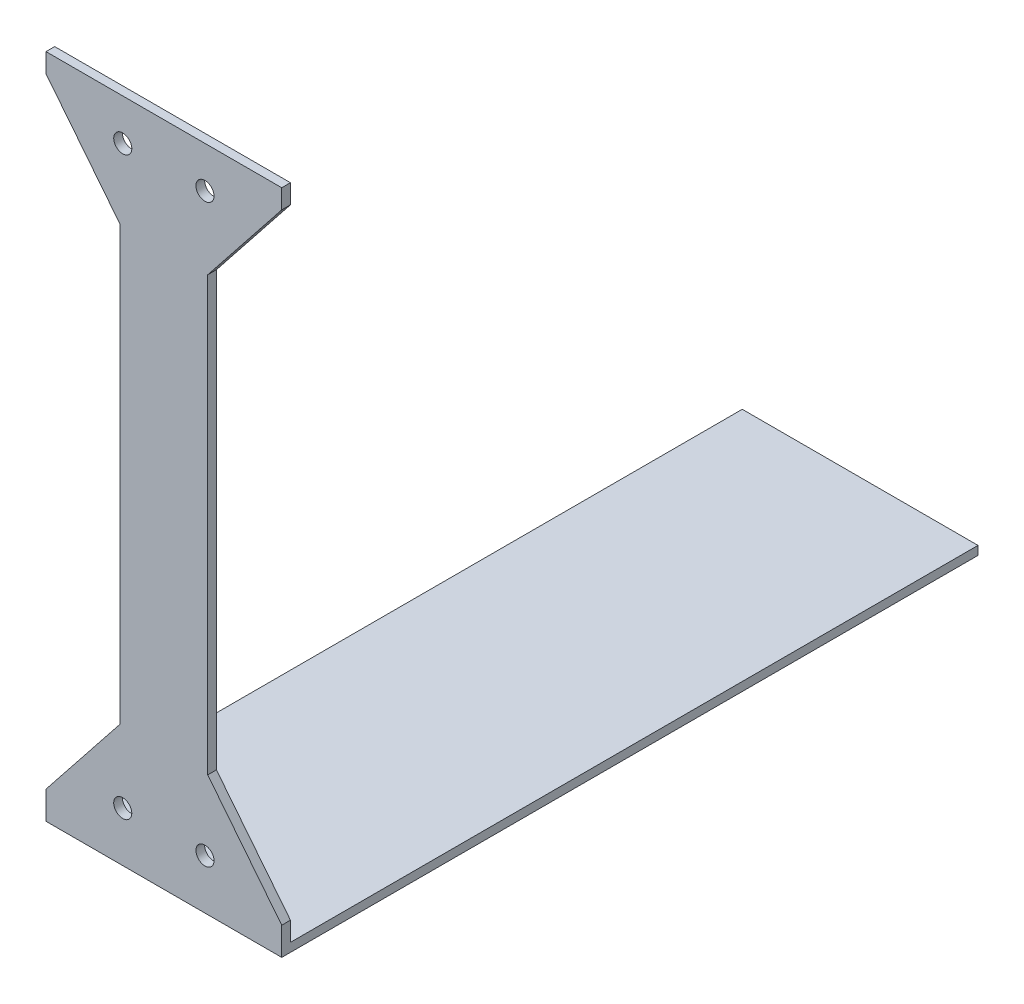
SolidWorks part; units mm, degrees
ref_plane "Front Plane" through (0, 0, 0) normal (0, 0, 1) x (1, 0, 0)
ref_plane "Top Plane" through (0, 0, 0) normal (0, 1, 0) x (1, 0, 0)
ref_plane "Right Plane" through (0, 0, 0) normal (1, 0, 0) x (0, 0, -1)
sketch "Sketch1" plane through (0, 0, 0) normal (0, 0, 1) x (1, 0, 0)
  line L0 (-117, 99.5) -> (-103.5, 116.5) construction
  line L1 (-146.5, 116.5) -> (-133, 99.5) construction
  line L2 (-133, 99.5) -> (-117, 99.5) construction
  line L3 (-117, 99.5) -> (-103.5, 116.5)
  line L4 (-146.5, 116.5) -> (-133, 99.5)
  line L5 (-133, 99.5) -> (-117, 99.5) construction
  line L6 (-250, 120) -> (0, 120) construction
  line L7 (-146.5, 120) -> (-103.5, 120)
  line L8 (0, 0) -> (-250, 0) construction
  line L9 (-103.5, 3.5) -> (-117, 20.5) construction
  line L10 (-117, 20.5) -> (-133, 20.5) construction
  line L11 (-133, 20.5) -> (-146.5, 3.5) construction
  line L12 (-103.5, 0) -> (-146.5, 0)
  line L13 (-103.5, 3.5) -> (-117, 20.5)
  line L14 (-117, 20.5) -> (-133, 20.5) construction
  line L15 (-133, 20.5) -> (-146.5, 3.5)
  line L16 (-103.5, 3.5) -> (-103.5, 0)
  line L18 (-146.5, 3.5) -> (-146.5, 0)
  line L19 (-103.5, 116.5) -> (-103.5, 120)
  line L20 (-146.5, 116.5) -> (-146.5, 120)
  line L21 (-117, 20.5) -> (-117, 99.5)
  line L22 (-133, 99.5) -> (-133, 20.5)
  arc A0 (-134.15, 112.5) -> (-130.85, 112.5) centre (-132.5, 112.5) ccw construction
  arc A1 (-130.85, 112.5) -> (-134.15, 112.5) centre (-132.5, 112.5) ccw construction
  arc A2 (-119.15, 112.5) -> (-115.85, 112.5) centre (-117.5, 112.5) ccw construction
  arc A3 (-115.85, 112.5) -> (-119.15, 112.5) centre (-117.5, 112.5) ccw construction
  arc A4 (-134.15, 112.5) -> (-130.85, 112.5) centre (-132.5, 112.5) ccw
  arc A5 (-130.85, 112.5) -> (-134.15, 112.5) centre (-132.5, 112.5) ccw
  arc A6 (-119.15, 112.5) -> (-115.85, 112.5) centre (-117.5, 112.5) ccw
  arc A7 (-115.85, 112.5) -> (-119.15, 112.5) centre (-117.5, 112.5) ccw
  arc A8 (-115.85, 7.5) -> (-119.15, 7.5) centre (-117.5, 7.5) ccw construction
  arc A9 (-119.15, 7.5) -> (-115.85, 7.5) centre (-117.5, 7.5) ccw construction
  arc A10 (-134.15, 7.5) -> (-130.85, 7.5) centre (-132.5, 7.5) ccw construction
  arc A11 (-130.85, 7.5) -> (-134.15, 7.5) centre (-132.5, 7.5) ccw construction
  arc A12 (-115.85, 7.5) -> (-119.15, 7.5) centre (-117.5, 7.5) ccw
  arc A13 (-119.15, 7.5) -> (-115.85, 7.5) centre (-117.5, 7.5) ccw
  arc A14 (-134.15, 7.5) -> (-130.85, 7.5) centre (-132.5, 7.5) ccw
  arc A15 (-130.85, 7.5) -> (-134.15, 7.5) centre (-132.5, 7.5) ccw
extrude "Boss-Extrude1" add sketch "Sketch1" along normal blind 1.5875
sketch "Sketch2" plane through (0, 0, 0) normal (0, 1, 0) x (1, 0, 0)
  line L0 (-103.5, -1.5875) -> (-103.5, 125.4125)
  line L1 (-103.5, 125.4125) -> (-146.5, 125.4125)
  line L2 (-146.5, 125.4125) -> (-146.5, -1.5875)
  line L4 (-146.5, -1.5875) -> (-103.5, -1.5875)
  dimension "D1" = 127
extrude "Boss-Extrude2" add sketch "Sketch2" against normal blind 1.5875
